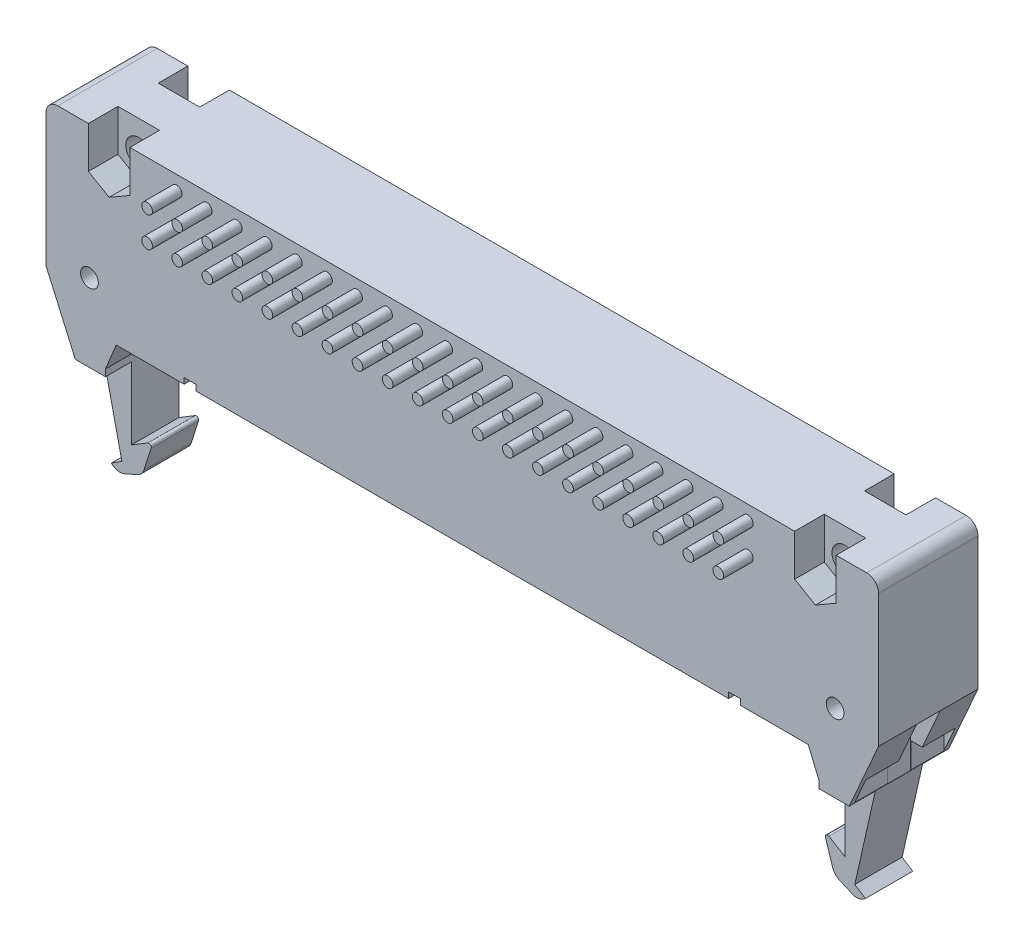
SolidWorks part; units mm, degrees
ref_plane "Спереди" through (0, 0, 0) normal (0, 0, 1) x (1, 0, 0)
ref_plane "Сверху" through (0, 0, 0) normal (0, 1, 0) x (1, 0, 0)
ref_plane "Справа" through (0, 0, 0) normal (1, 0, 0) x (0, 0, -1)
sketch "Эскиз1" plane through (0, 0, 0) normal (0, 0, 1) x (1, 0, 0)
  line L0 (0, 8.2919) -> (0, -18.517) construction
  line L1 (49.2464, 0) -> (-43.5201, 0) construction
  line L2 (-30.1461, -11.8582) -> (-29.2322, -9.653)
  line L3 (-29.2322, -9.653) -> (29.2322, -9.653)
  line L4 (-30.1461, -18.517) -> (-30.1461, -11.8582)
  line L5 (-34.17, 5.3815) -> (34.17, 5.3815)
  line L6 (35.17, -6.8161) -> (35.17, 4.3815)
  line L7 (-32.6906, -12.4303) -> (-35.17, -6.8161)
  line L8 (30.1461, -18.517) -> (28.7759, -17.6849)
  line L9 (28.4816, -17.9169) -> (29.0951, -19.8329)
  line L10 (29.6435, -20.4427) -> (30.7209, -20.9185)
  line L11 (31.7186, -20.8085) -> (31.8561, -20.707)
  line L12 (31.8561, -20.707) -> (30.9604, -20.1256)
  line L13 (30.9604, -20.1256) -> (32.6906, -12.4303)
  line L14 (32.6906, -12.4303) -> (35.17, -6.8161)
  line L15 (30.1461, -18.517) -> (30.1461, -11.8582)
  line L16 (30.1461, -11.8582) -> (29.2322, -9.653)
  line L17 (-30.9604, -20.1256) -> (-32.6906, -12.4303)
  line L18 (-31.8561, -20.707) -> (-30.9604, -20.1256)
  line L19 (-31.7186, -20.8085) -> (-31.8561, -20.707)
  line L20 (-29.6435, -20.4427) -> (-30.7209, -20.9185)
  line L21 (-28.4816, -17.9169) -> (-29.0951, -19.8329)
  line L22 (-30.1461, -18.517) -> (-28.7759, -17.6849)
  line L23 (-35.17, -6.8161) -> (-35.17, 4.3815)
  arc A0 (29.0951, -19.8329) -> (29.6435, -20.4427) centre (30.0475, -19.5279) ccw
  arc A1 (30.7209, -20.9185) -> (31.7186, -20.8085) centre (31.1249, -20.0038) ccw
  arc A2 (28.7759, -17.6849) -> (28.4816, -17.9169) centre (28.6721, -17.8559) ccw
  arc A3 (34.17, 5.3815) -> (35.17, 4.3815) centre (34.17, 4.3815) cw
  arc A4 (-34.17, 5.3815) -> (-35.17, 4.3815) centre (-34.17, 4.3815) ccw
  arc A5 (-28.7759, -17.6849) -> (-28.4816, -17.9169) centre (-28.6721, -17.8559) cw
  arc A6 (-30.7209, -20.9185) -> (-31.7186, -20.8085) centre (-31.1249, -20.0038) cw
  arc A7 (-29.0951, -19.8329) -> (-29.6435, -20.4427) centre (-30.0475, -19.5279) cw
  point P27 (0, 5.3815)
  point P45 (0, -9.653)
  dimension "D1" = 35.17
extrude "Вытянуть1" add sketch "Эскиз1" along normal blind 8.4
sketch "Эскиз2" plane through (35.17, 0, 0) normal (1, 0, 0) x (0, 0, -1)
  line L0 (-4.2, 8.0464) -> (-4.2, -24.3467) construction
  line L4 (-10.0759, -23.066) -> (-6.2, -23.066)
  line L5 (-10.0759, -23.066) -> (-10.0759, -12.4303)
  line L6 (-10.0759, -12.4303) -> (-6.2, -12.4303)
  line L7 (-6.2, -23.066) -> (-6.2, -12.4303)
  line L8 (-2.2, -23.066) -> (-2.2, -12.4303)
  line L9 (1.6759, -12.4303) -> (-2.2, -12.4303)
  line L10 (1.6759, -23.066) -> (1.6759, -12.4303)
  line L11 (1.6759, -23.066) -> (-2.2, -23.066)
  line L12 (-8.4, -12.4303) -> (0, -12.4303) construction
  dimension "D1" = 2
extrude "Вырез-Вытянуть1" cut sketch "Эскиз2" against normal blind 150
sketch "Эскиз3" plane through (35.17, 0, 0) normal (1, 0, 0) x (0, 0, -1)
  line L0 (-4.2, -21.7791) -> (-4.2, -1.2196) construction
  line L4 (-5.2, -12.4303) -> (-3.2, -12.4303)
  line L5 (-5.2, -12.4303) -> (-5.2, -6.8161)
  line L6 (-5.2, -6.8161) -> (-3.2, -6.8161)
  line L7 (-3.2, -12.4303) -> (-3.2, -6.8161)
  line L9 (-8.4, -6.8161) -> (-8.4, 4.3815) construction
  line L10 (0, -6.8161) -> (0, 4.3815) construction
  line L11 (-8.4, -6.8161) -> (0, -6.8161) construction
  line L12 (-8.4, -12.4303) -> (-6.2, -12.4303) construction
  dimension "D1" = 2
extrude "Вырез-Вытянуть2" cut sketch "Эскиз3" against normal blind 2.5
sketch "Эскиз4" plane through (35.17, 0, 0) normal (1, 0, 0) x (0, 0, -1)
  line L0 (-4.2, -13.7122) -> (-4.2, -4.7037) construction
  line L4 (-7.9666, -12.4303) -> (-0.4334, -12.4303)
  line L5 (-7.9666, -12.4303) -> (-7.9666, -10.2303)
  line L6 (-7.9666, -10.2303) -> (-0.4334, -10.2303)
  line L7 (-0.4334, -12.4303) -> (-0.4334, -10.2303)
  line L8 (-8.4, -12.4303) -> (-8.4, -6.8161) construction
  line L9 (0, -12.4303) -> (0, -6.8161) construction
  line L10 (-8.4, -12.4303) -> (-6.2, -12.4303) construction
  dimension "D1" = 2.2
extrude "Вырез-Вытянуть3" cut sketch "Эскиз4" against normal offset from surface (2.45 mm away) 0.05 up to face at (32.67, -9.6232, 4.2)
sketch "Эскиз5" plane through (-35.17, 0, 0) normal (-1, 0, 0) x (0, 0, 1)
  line L4 (5.2, -12.4303) -> (5.2, -6.8161)
  line L5 (3.2, -12.4303) -> (5.2, -12.4303)
  line L6 (3.2, -6.8161) -> (3.2, -12.4303)
  line L7 (5.2, -6.8161) -> (3.2, -6.8161)
  line L8 (5.2, -12.4303) -> (5.2, -6.8161)
  line L9 (3.2, -12.4303) -> (5.2, -12.4303)
  line L10 (3.2, -6.8161) -> (3.2, -12.4303)
  line L11 (5.2, -6.8161) -> (3.2, -6.8161)
  dimension "D1" = 0
extrude "Вырез-Вытянуть4" cut sketch "Эскиз5" against normal blind 2.5
sketch "Эскиз6" plane through (-35.17, 0, 0) normal (-1, 0, 0) x (0, 0, 1)
  line L4 (5.2, -10.2303) -> (5.2, -12.3637)
  line L5 (7.9666, -10.2303) -> (5.2, -10.2303)
  line L6 (7.9666, -12.3637) -> (7.9666, -10.2303)
  line L7 (5.2, -12.3637) -> (7.9666, -12.3637)
  line L8 (5.2, -10.2303) -> (5.2, -12.3637)
  line L9 (7.9666, -10.2303) -> (5.2, -10.2303)
  line L10 (7.9666, -12.3637) -> (7.9666, -10.2303)
  line L11 (5.2, -12.3637) -> (7.9666, -12.3637)
  line L12 (0.4334, -10.2303) -> (0.4334, -12.3637)
  line L13 (3.2, -10.2303) -> (0.4334, -10.2303)
  line L14 (3.2, -12.3637) -> (3.2, -10.2303)
  line L15 (0.4334, -12.3637) -> (3.2, -12.3637)
  line L16 (0.4334, -10.2303) -> (0.4334, -12.3637)
  line L17 (3.2, -10.2303) -> (0.4334, -10.2303)
  line L18 (3.2, -12.3637) -> (3.2, -10.2303)
  line L19 (0.4334, -12.3637) -> (3.2, -12.3637)
  dimension "D1" = 0
  dimension "D2" = 0
extrude "Вырез-Вытянуть5" cut sketch "Эскиз6" against normal offset from surface (2.45 mm away) 0.05 up to face at (-32.67, -9.6232, 4.2)
sketch "Эскиз7" plane through (0, -9.653, 0) normal (0, -1, 0) x (1, 0, 0)
  line L0 (-16.9344, 4.2) -> (17.0384, 4.2) construction
  line L4 (-29.2322, 1.45) -> (29.2322, 1.45)
  line L5 (-29.2322, 1.45) -> (-29.2322, 6.95)
  line L6 (-29.2322, 6.95) -> (29.2322, 6.95)
  line L7 (29.2322, 1.45) -> (29.2322, 6.95)
  line L8 (-29.2322, 8.4) -> (-29.2322, 0) construction
  line L9 (29.2322, 8.4) -> (29.2322, 0) construction
  dimension "D1" = 5.5
extrude "Вырез-Вытянуть6" cut sketch "Эскиз7" against normal blind 10
sketch "Эскиз8" plane through (0, 0.347, 0) normal (0, -1, 0) x (1, 0, 0)
  line L0 (-5.9309, 4.2) -> (6.6853, 4.2) construction
  line L3 (29.2322, 6.95) -> (-29.2322, 6.95) construction
  line L4 (-29.2322, 1.45) -> (29.2322, 1.45) construction
  circle A0 centre (6.35, 2.93) radius 0.45
  circle A1 centre (6.35, 5.47) radius 0.45
  circle A2 centre (1.27, 5.47) radius 0.45
  circle A3 centre (1.27, 2.93) radius 0.45
  circle A4 centre (3.81, 5.47) radius 0.45
  circle A5 centre (3.81, 2.93) radius 0.45
  circle A6 centre (-1.27, 5.47) radius 0.45
  circle A7 centre (-1.27, 2.93) radius 0.45
  circle A8 centre (-3.81, 5.47) radius 0.45
  circle A9 centre (-3.81, 2.93) radius 0.45
  circle A10 centre (-1.27, 2.93) radius 0.45 [skipped]
  circle A11 centre (1.27, 2.93) radius 0.45 [skipped]
  circle A12 centre (-1.27, 5.47) radius 0.45 [skipped]
  circle A13 centre (1.27, 5.47) radius 0.45 [skipped]
  circle A14 centre (8.89, 2.93) radius 0.45
  circle A15 centre (8.89, 5.47) radius 0.45
  circle A16 centre (11.43, 2.93) radius 0.45
  circle A17 centre (11.43, 5.47) radius 0.45
  circle A18 centre (-6.35, 5.47) radius 0.45
  circle A19 centre (-6.35, 2.93) radius 0.45
  circle A20 centre (-8.89, 5.47) radius 0.45
  circle A21 centre (-8.89, 2.93) radius 0.45
  circle A22 centre (-11.43, 5.47) radius 0.45
  circle A23 centre (-11.43, 2.93) radius 0.45
  circle A24 centre (-13.97, 2.93) radius 0.45
  circle A25 centre (-13.97, 5.47) radius 0.45
  circle A26 centre (-16.51, 2.93) radius 0.45
  circle A27 centre (-16.51, 5.47) radius 0.45
  circle A28 centre (-19.05, 2.93) radius 0.45
  circle A29 centre (-19.05, 5.47) radius 0.45
  circle A30 centre (-21.59, 2.93) radius 0.45
  circle A31 centre (-21.59, 5.47) radius 0.45
  circle A32 centre (-24.13, 2.93) radius 0.45
  circle A33 centre (-24.13, 5.47) radius 0.45
  circle A34 centre (13.97, 2.93) radius 0.45
  circle A35 centre (13.97, 5.47) radius 0.45
  circle A36 centre (16.51, 2.93) radius 0.45
  circle A37 centre (16.51, 5.47) radius 0.45
  circle A38 centre (19.05, 2.93) radius 0.45
  circle A39 centre (19.05, 5.47) radius 0.45
  circle A40 centre (21.59, 2.93) radius 0.45
  circle A41 centre (21.59, 5.47) radius 0.45
  circle A42 centre (24.13, 2.93) radius 0.45
  circle A43 centre (24.13, 5.47) radius 0.45
  dimension "D1" = 2.54
  dimension "D2" = 2.54
  dimension "D3" = 3.81
  dimension "D4" = 3.81
  dimension "D5" = 0.9
extrude "Вытянуть2" add sketch "Эскиз8" along normal blind 8
sketch "Эскиз9" plane through (0, 0, 0) normal (0, 0, -1) x (-1, 0, 0)
  line L0 (0, 7.8731) -> (0, -14.2295) construction
  line L4 (-29.835, 2.8815) -> (29.835, 2.8815) construction
  line L5 (-32.3588, -5.8676) -> (-8.0682, -5.8676) construction
  line L6 (22.5, -10.1387) -> (22.5, -9.1642)
  line L7 (-23.5, -10.1387) -> (-22.5, -10.1387)
  line L8 (-23.5, -10.1387) -> (-23.5, -9.1642)
  line L9 (-23.5, -9.1642) -> (-22.5, -9.1642)
  line L10 (-22.5, -10.1387) -> (-22.5, -9.1642)
  line L11 (23.5, -9.1642) -> (22.5, -9.1642)
  line L12 (23.5, -10.1387) -> (23.5, -9.1642)
  line L13 (23.5, -10.1387) -> (22.5, -10.1387)
  line L14 (-35.17, -6.8161) -> (-35.17, 4.3815) construction
  line L15 (35.17, 4.3815) -> (35.17, -6.8161) construction
  circle A0 centre (-29.835, 2.8815) radius 1.1
  circle A1 centre (29.835, 2.8815) radius 1.1
  circle A2 centre (-31.5, -5.8676) radius 0.75
  circle A3 centre (31.5, -5.8676) radius 0.75
  dimension "D1" = 59.67
  dimension "D2" = 45
  dimension "D3" = 2.2
  dimension "D4" = 1.5
  dimension "D5" = 31.5
  dimension "D6" = 1
extrude "Вырез-Вытянуть7" cut sketch "Эскиз9" against normal blind 10
sketch "Эскиз10" plane through (0, 0, 0) normal (0, 0, -1) x (-1, 0, 0)
  line L0 (0, -4.0596) -> (0, 7.1047) construction
  line L1 (-31.5894, 3.9876) -> (-31.5894, 6.5566)
  line L2 (-31.5894, 6.5566) -> (-28.0806, 6.5566)
  line L3 (-31.5894, 3.9876) -> (-31.5894, 1.8685)
  line L4 (-31.5894, 1.8685) -> (-29.835, 0.8556)
  line L5 (-29.835, 0.8556) -> (-28.0806, 1.8685)
  line L6 (-28.0806, 1.8685) -> (-28.0806, 3.9876)
  line L7 (-28.0806, 6.5566) -> (-28.0806, 3.9876)
  line L8 (-30.2548, 4.665) -> (-31.132, 4.1585) [skipped]
  line L9 (-28.5811, 4.1834) -> (-29.4583, 4.6898) [skipped]
  line L10 (28.0806, 6.5566) -> (28.0806, 3.9876)
  line L11 (28.0806, 1.8685) -> (28.0806, 3.9876)
  line L12 (29.835, 0.8556) -> (28.0806, 1.8685)
  line L13 (31.5894, 1.8685) -> (29.835, 0.8556)
  line L14 (31.5894, 3.9876) -> (31.5894, 1.8685)
  line L15 (31.5894, 6.5566) -> (28.0806, 6.5566)
  line L16 (31.5894, 3.9876) -> (31.5894, 6.5566)
  line L17 (-29.835, 0.8556) -> (-29.835, 5.3815) construction
  line L20 (-26, 1.8685) -> (26, 1.8685)
  line L21 (-26, 1.8685) -> (-26, 3.8685)
  line L22 (-26, 3.8685) -> (26, 3.8685)
  line L23 (26, 1.8685) -> (26, 3.8685)
  circle A0 centre (-29.835, 2.8815) radius 1.7544 construction
  circle A1 centre (29.835, 2.8815) radius 1.7544 construction
  dimension "D1" = 2
  dimension "D2" = 59.67
  dimension "D3" = 52
extrude "Вырез-Вытянуть8" cut sketch "Эскиз10" against normal blind 2.5
sketch "Эскиз11" plane through (0, 0, 8.4) normal (0, 0, 1) x (1, 0, 0)
  line L5 (31.5894, 1.8685) -> (31.5894, 5.3815)
  line L6 (29.835, 0.8556) -> (31.5894, 1.8685)
  line L7 (28.0806, 1.8685) -> (29.835, 0.8556)
  line L8 (28.0806, 5.3815) -> (28.0806, 1.8685)
  line L9 (31.5894, 5.3815) -> (28.0806, 5.3815)
  line L10 (31.5894, 1.8685) -> (31.5894, 5.3815)
  line L11 (29.835, 0.8556) -> (31.5894, 1.8685)
  line L12 (28.0806, 1.8685) -> (29.835, 0.8556)
  line L13 (28.0806, 5.3815) -> (28.0806, 1.8685)
  line L14 (31.5894, 5.3815) -> (28.0806, 5.3815)
  line L15 (-28.0806, 5.3815) -> (-31.5894, 5.3815)
  line L16 (-28.0806, 5.3815) -> (-31.5894, 5.3815)
  line L24 (-28.0806, 1.8685) -> (-28.0806, 5.3815)
  line L25 (-29.835, 0.8556) -> (-28.0806, 1.8685)
  line L26 (-31.5894, 1.8685) -> (-29.835, 0.8556)
  line L27 (-31.5894, 5.3815) -> (-31.5894, 1.8685)
  line L29 (-28.0806, 1.8685) -> (-28.0806, 5.3815)
  line L30 (-29.835, 0.8556) -> (-28.0806, 1.8685)
  line L31 (-31.5894, 1.8685) -> (-29.835, 0.8556)
  line L32 (-31.5894, 5.3815) -> (-31.5894, 1.8685)
  dimension "D1" = 0
  dimension "D3" = 0
extrude "Вырез-Вытянуть9" cut sketch "Эскиз11" against normal blind 2.5
sketch "Эскиз12" plane through (0, 0, 0) normal (0, 0, -1) x (-1, 0, 0)
  line L0 (0, 0) -> (0, -11.6719) construction
  line L2 (-2.3, -10.95) -> (2.3, -10.95)
  line L3 (-2.3, -10.95) -> (-2.3, -1.653)
  line L4 (-2.3, -1.653) -> (2.3, -1.653)
  line L5 (2.3, -10.95) -> (2.3, -1.653)
  line L6 (22.5, -9.653) -> (-22.5, -9.653) construction
  dimension "D1" = 4.6
  dimension "D2" = 8
extrude "Вырез-Вытянуть10" cut sketch "Эскиз12" against normal up to surface (1.45 mm away) up to face at (0, -7.8234, 1.45)
chamfer "Фаска1" distance 2 angle 45 1 edges at (0, -1.653, 0)
sketch "Эскиз13" plane through (0, 0, 0) normal (0, 0, -1) x (-1, 0, 0)
  line L0 (25.2117, -9.653) -> (26.1752, -9.653)
  line L2 (29.2322, -9.653) -> (23.5, -9.653) construction
  line L5 (26.1752, -9.653) -> (25.6934, -8.8186)
  line L6 (25.6934, -8.8186) -> (25.2117, -9.653)
extrude "Вырез-Вытянуть11" cut sketch "Эскиз13" against normal blind 0.2
sketch "Эскиз14" plane through (0, 0, 8.4) normal (0, 0, 1) x (1, 0, 0)
  line L0 (-29.835, 2.8815) -> (10.9546, 2.8815) construction
  line L1 (0, -2.2554) -> (0, 5.0268) construction
  circle A0 centre (6.35, 4.1515) radius 0.45
  circle A1 centre (6.35, 1.6115) radius 0.45
  circle A2 centre (1.27, 4.1515) radius 0.45
  circle A3 centre (1.27, 1.6115) radius 0.45
  circle A4 centre (3.81, 4.1515) radius 0.45
  circle A5 centre (3.81, 1.6115) radius 0.45
  circle A6 centre (-1.27, 4.1515) radius 0.45
  circle A7 centre (-1.27, 1.6115) radius 0.45
  circle A8 centre (-3.81, 4.1515) radius 0.45
  circle A9 centre (-3.81, 1.6115) radius 0.45
  circle A10 centre (-1.27, 1.6115) radius 0.45 [skipped]
  circle A11 centre (1.27, 1.6115) radius 0.45 [skipped]
  circle A12 centre (-1.27, 4.1515) radius 0.45 [skipped]
  circle A13 centre (1.27, 4.1515) radius 0.45 [skipped]
  circle A14 centre (8.89, 4.1515) radius 0.45
  circle A15 centre (8.89, 1.6115) radius 0.45
  circle A16 centre (11.43, 4.1515) radius 0.45
  circle A17 centre (11.43, 1.6115) radius 0.45
  circle A18 centre (-6.35, 1.6115) radius 0.45
  circle A19 centre (-6.35, 4.1515) radius 0.45
  circle A20 centre (-8.89, 1.6115) radius 0.45
  circle A21 centre (-8.89, 4.1515) radius 0.45
  circle A22 centre (-11.43, 1.6115) radius 0.45
  circle A23 centre (-11.43, 4.1515) radius 0.45
  circle A24 centre (13.97, 1.6115) radius 0.45
  circle A25 centre (13.97, 4.1515) radius 0.45
  circle A26 centre (16.51, 1.6115) radius 0.45
  circle A27 centre (16.51, 4.1515) radius 0.45
  circle A28 centre (19.05, 1.6115) radius 0.45
  circle A29 centre (19.05, 4.1515) radius 0.45
  circle A30 centre (21.59, 1.6115) radius 0.45
  circle A31 centre (21.59, 4.1515) radius 0.45
  circle A32 centre (24.13, 1.6115) radius 0.45
  circle A33 centre (24.13, 4.1515) radius 0.45
  circle A34 centre (-13.97, 1.6115) radius 0.45
  circle A35 centre (-13.97, 4.1515) radius 0.45
  circle A36 centre (-16.51, 1.6115) radius 0.45
  circle A37 centre (-16.51, 4.1515) radius 0.45
  circle A38 centre (-19.05, 1.6115) radius 0.45
  circle A39 centre (-19.05, 4.1515) radius 0.45
  circle A40 centre (-21.59, 1.6115) radius 0.45
  circle A41 centre (-21.59, 4.1515) radius 0.45
  circle A42 centre (-24.13, 1.6115) radius 0.45
  circle A43 centre (-24.13, 4.1515) radius 0.45
  dimension "D1" = 2.54
  dimension "D2" = 2.54
extrude "Вытянуть3" add sketch "Эскиз14" along normal blind 2.5
